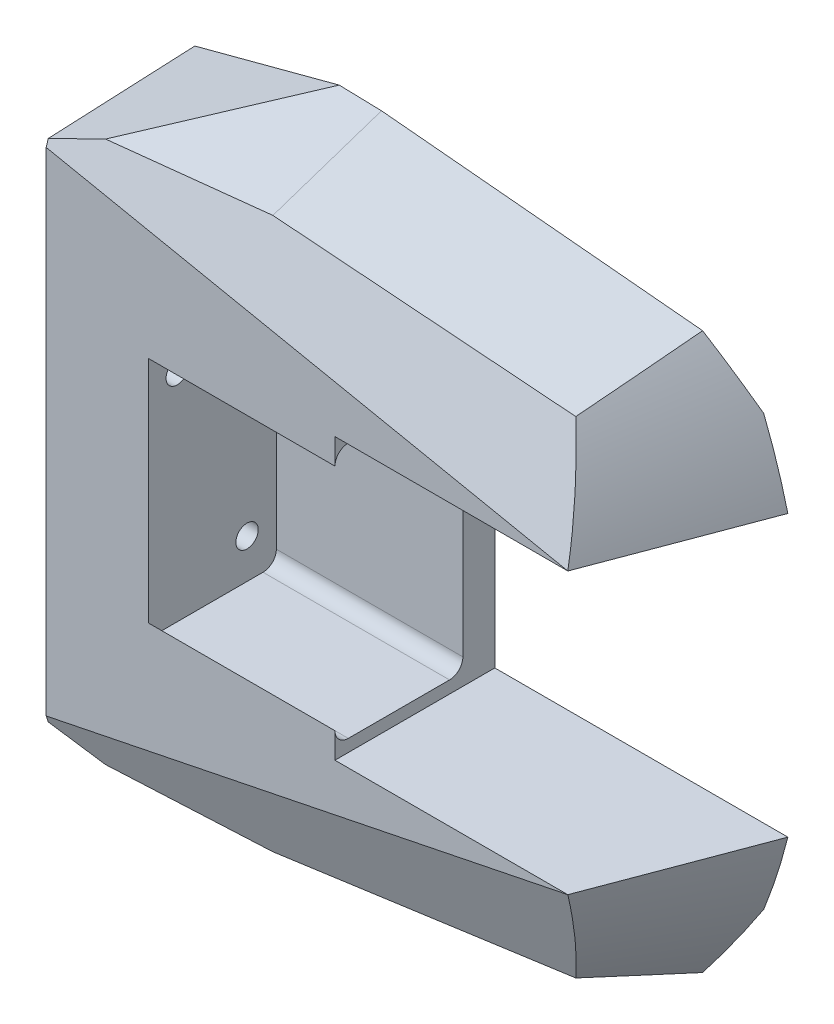
SolidWorks part; units mm, degrees
material "7075-O (SS)"
ref_plane "Top Plane" through (0, 0, 0) normal (0, 0, 1) x (1, 0, 0)
ref_plane "Front Plane" through (0, 0, 0) normal (0, 1, 0) x (1, 0, 0)
ref_plane "Right Plane" through (0, 0, 0) normal (1, 0, 0) x (0, 0, -1)
sketch "Sketch2" plane through (0, 0, 0) normal (0, 0, 1) x (1, 0, 0)
  line L0 (-50, 46.6303) -> (-41.2217, 50)
  line L1 (50, -50) -> (-50, -50)
  line L2 (50, -50) -> (50, 50)
  line L3 (50, 50) -> (-50, 50)
  line L4 (-50, -50) -> (-50, 50)
  line L5 (50, -50) -> (-50, 50) construction
  line L6 (50, 50) -> (-50, -50) construction
  line L7 (-10.1637, 50) -> (50, 42.6128)
  line L8 (-50, 0) -> (50, 0) construction
  line L9 (-10.1637, -50) -> (50, -42.6128)
  line L10 (-50, -46.6303) -> (-41.2217, -50)
  line L11 (50, 26.3007) -> (26.3007, 26.3007)
  line L12 (50, -26.3007) -> (26.3007, -26.3007)
  line L13 (26.3007, -26.3007) -> (26.3007, 26.3007)
  arc A0 (43.4207, 43.4207) -> (43.4207, -43.4207) centre (-44, 0) cw
  point P0 (0, 0)
  point P19 (50, -26.3007)
  point P20 (50, 26.3007)
  dimension "D1" = 100
  dimension "D2" = 100
  dimension "D3" = 69
  dimension "D4" = 3.3697
  dimension "D5" = 83
  dimension "D6" = 7.3872
  dimension "D7" = 44
extrude "Boss-Extrude1" add sketch "Sketch2" along normal blind 30 contours A0 L12 L13 L11 L7 L3 L0 L4 L10 L1 L9 region at (-7.835, 0, 0)
sketch "Sketch3" plane through (26.3007, 0, 0) normal (1, 0, 0) x (0, 0, -1)
  line L0 (-30, 26.3007) -> (0, 26.3007) construction
  line L1 (-30, -26.3007) -> (0, -26.3007)
  line L2 (-30, -26.3007) -> (-30, 26.3007)
  line L3 (-30, 26.3007) -> (0, 26.3007)
  line L4 (0, -26.3007) -> (0, 26.3007)
extrude "Cut-Extrude1" cut sketch "Sketch3" against normal blind 20
draft "Draft1" type of draft neutral plane draft angle 20 faces to draft 6 face at (-25.6927, 50, 15) face at (16.6285, 46.7103, 15) face at (46.9118, 34.9381, 15) face at (46.9118, -34.9381, 15) face at (-25.6927, -50, 15) face at (16.6285, -46.7103, 15) neutral plane through (0, 0, 30) neutral plane normal (0, 0, 1) parameters "D1"=20
sketch "Sketch5" plane through (-50, 0, 0) normal (-1, 0, 0) x (0, 0, 1)
  line L0 (0, -46.6303) -> (0, 46.6303) construction
  line L9 (0, 42) -> (23, 42)
  line L10 (0, 42) -> (0, -42)
  line L11 (0, -42) -> (23, -42)
  line L12 (28, 37) -> (28, -37)
  arc A0 (28, -37) -> (23, -42) centre (23, -37) cw
  arc A1 (28, 37) -> (23, 42) centre (23, 37) ccw
  point P15 (28, -42)
  point P18 (28, 42)
  dimension "D4" = 5
  dimension "D1" = 42
  dimension "D2" = 84
  dimension "D3" = 28
extrude "Cut-Extrude2" cut sketch "Sketch5" against normal blind 5
sketch "Sketch6" plane through (0, 0, 0) normal (0, 0, -1) x (-1, 0, 0)
  line L1 (45, 42) -> (10, 42)
  line L2 (45, 42) -> (45, -42)
  line L3 (45, -42) -> (10, -42)
  line L4 (5, 37) -> (5, -37)
  arc A0 (10, -42) -> (5, -37) centre (10, -37) cw
  arc A1 (10, 42) -> (5, 37) centre (10, 37) ccw
  point P7 (5, -42)
  point P10 (5, 42)
  dimension "D3" = 5
  dimension "D1" = 40
  dimension "D2" = 84
extrude "Cut-Extrude3" cut sketch "Sketch6" against normal blind 5
sketch "Sketch7" plane through (0, 0, 5) normal (0, 0, -1) x (-1, 0, 0)
  point P0 (29.9, 29.8957)
  point P3 (29.9, -29.8957)
hole_wizard "M6x1.0 Tapped Hole1" positions "Sketch7" profile "Sketch8" tap size "M6x1.0" standard "ANSI Metric"
sketch "Sketch8" plane through (-29.9, 29.8957, 5) normal (1, 0, 0) x (0, 1, 0)
  line L0 (0, 0) -> (0, 11.5022)
  line L1 (0, 11.5022) -> (2.5, 10)
  line L2 (2.5, 10) -> (2.5, 0)
  line L5 (2.5, 0) -> (0, 0)
  line L10 (0, 11.5022) -> (-2.5, 10) construction
  line L11 (0, -6.35) -> (0, 107.95) construction
  dimension "Tap Drill Dia." = 5
  dimension "Tap Drill Depth" = 10
  dimension "Drill Angle" = 118
cosmetic thread "Hole Thread1" parameters "D1"=12, "D2"=6
cosmetic thread "Hole Thread2" parameters "D1"=12, "D2"=6
sketch "Sketch9" plane through (0, 0, 0) normal (0, 0, -1) x (-1, 0, 0)
  line L0 (50, 46.6303) -> (-56.7679, 40.304)
  line L4 (50, 46.6303) -> (18.1671, 64.9129)
  line L5 (18.1671, 64.9129) -> (-51.4723, 56.583)
  arc A0 (-50.3888, 53.5662) -> (-61.2941, 26.3007) centre (44, 0) ccw construction
  arc A3 (-56.7679, 40.304) -> (-51.4723, 56.583) centre (56.438, 12.4787) cw
revolve "Cut-Revolve1" cut sketch "Sketch9" angle 20 about L0
sketch "Sketch11" plane through (0, 0, 0) normal (0, 0, -1) x (-1, 0, 0)
  line L0 (50, -46.6303) -> (-56.7679, -40.304)
  line L1 (50, -46.6303) -> (21.2236, -65.429)
  line L2 (21.2236, -65.429) -> (-53.454, -56.7727)
  arc A0 (-61.2941, -26.3007) -> (-50.3888, -53.5662) centre (44, 0) ccw construction
  arc A1 (-53.454, -56.7727) -> (-56.7679, -40.304) centre (59.1366, -25.5487) cw
revolve "Cut-Revolve2" cut sketch "Sketch11" angle 20 about L0 reverse direction yes
sketch "Sketch13" plane through (0, 0, 30) normal (0, 0, 1) x (1, 0, 0)
  line L0 (-50, 46.6303) -> (50, 26.3007)
  line L1 (50, 26.3007) -> (49.447, 52.16)
  line L2 (49.447, 52.16) -> (-50, 58.9949)
  line L3 (-50, 58.9949) -> (-50, 46.6303)
revolve "Cut-Revolve3" cut sketch "Sketch13" angle 20 about L0 reverse direction yes
sketch "Sketch14" plane through (0, 0, 30) normal (0, 0, 1) x (1, 0, 0)
  line L5 (50, -26.3007) -> (49.447, -52.16)
  line L6 (50, -26.3007) -> (-50, -46.6303)
  line L7 (-50, -46.6303) -> (-50, -58.9953)
  line L8 (-50, -58.9953) -> (49.447, -52.16)
  dimension "D1" = 12.365
revolve "Cut-Revolve4" cut sketch "Sketch14" angle 20 about L6 reverse direction yes
sketch "Sketch15" plane through (6.3007, 0, 0) normal (1, 0, 0) x (0, 0, -1)
  line L18 (-30, 0) -> (-30, -21.5)
  line L19 (-30, 26.3007) -> (-30, -26.3007) construction
  line L20 (-27.5, -24) -> (-8.5, -24)
  line L21 (-6, -21.5) -> (-6, 21.5)
  line L22 (-8.5, 24) -> (-27.5, 24)
  line L23 (-30, 21.5) -> (-30, 0)
  arc A0 (-8.5, -24) -> (-6, -21.5) centre (-8.5, -21.5) ccw
  arc A1 (-6, 21.5) -> (-8.5, 24) centre (-8.5, 21.5) ccw
  arc A2 (-27.5, 24) -> (-30, 21.5) centre (-27.5, 21.5) ccw
  arc A3 (-30, -21.5) -> (-27.5, -24) centre (-27.5, -21.5) ccw
  point P9 (-6, -24)
  point P14 (-30, 24)
  point P17 (-30, -24)
  dimension "D4" = 2.5
  dimension "D1" = 24
  dimension "D2" = 24
  dimension "D3" = 24
extrude "Cut-Extrude4" cut sketch "Sketch15" against normal blind 35
sketch "Sketch16" plane through (-28.6993, 0, 0) normal (1, 0, 0) x (0, 0, -1)
  point P0 (-11.498, -16.6054)
  point P3 (-24.602, 16.6054)
hole_wizard "M5x0.8 Tapped Hole1" positions "Sketch16" profile "Sketch17" tap size "M5x0.8" standard "ANSI Metric" end condition through all
sketch "Sketch17" plane through (-28.6993, -16.6054, 11.498) normal (0, 1, 0) x (0, 0, -1)
  line L0 (0, 0) -> (0, 21.3007)
  line L1 (0, 21.3007) -> (2.1, 21.3007)
  line L2 (2.1, 21.3007) -> (2.1, 0)
  line L5 (2.1, 0) -> (0, 0)
  line L11 (0, -6.35) -> (0, 107.95) construction
  dimension "Thru Tap Drill Dia." = 4.2
  dimension "Thru Tap Drill Depth" = 21.3007
cosmetic thread "Hole Thread3" parameters "D2"=5
cosmetic thread "Hole Thread4" parameters "D2"=5
sketch "Sketch19" plane through (-50, 0, 0) normal (-1, 0, 0) x (0, 0, 1)
  line L1 (0, 58.8905) -> (47.5161, 58.8905)
  line L2 (0, 58.8905) -> (0, -58.8905)
  line L3 (0, -58.8905) -> (47.5161, -58.8905)
  line L4 (47.5161, 58.8905) -> (47.5161, -58.8905)
revolve "Cut-Revolve5" cut sketch "Sketch19" angle 4 about L2 reverse direction yes
sketch "Sketch20" plane through (0, 0, 0) normal (0, 0, -1) x (-1, 0, 0)
  arc A0 (-56.7679, 40.304) -> (-61.2941, 26.3007) centre (44, 0) ccw construction
  arc A1 (-61.2941, -26.3007) -> (-56.7679, -40.304) centre (44, 0) ccw construction
  point P0 (-50.2687, 33.3791)
  point P2 (-50.2687, -33.3791)
  point P4 (-36.2687, -33.3791)
  point P6 (-22.2687, -33.3791)
  point P8 (-36.2687, 33.3791)
  point P10 (-22.2687, 33.3791)
  point P16 (-59.2687, 33.3791)
  point P20 (-59.2687, -33.3791)
  dimension "D1" = 9
  dimension "D2" = 14
  dimension "D3" = 14
  dimension "D4" = 9
  dimension "D5" = 14
  dimension "D6" = 14
  dimension "D7" = 66.7583
hole_wizard "CSK for M5 Flat Head Machine Screw1" positions "Sketch20" profile "Sketch21" countersink size "M5" standard "ANSI Metric"
sketch "Sketch21" plane through (50.2687, 33.3791, 0) normal (1, 0, 0) x (0, 1, 0)
  line L0 (0, 0) -> (0, 11.6524)
  line L1 (0, 11.6524) -> (2.75, 10)
  line L2 (2.75, 10) -> (2.75, 2.45)
  line L3 (2.75, 2.45) -> (5.2, 0)
  line L5 (5.2, 0) -> (0, 0)
  line L6 (-2.75, 2.45) -> (-5.2, 0) construction
  line L10 (0, 11.6524) -> (-2.75, 10) construction
  line L11 (0, -6.35) -> (0, 107.95) construction
  dimension "Hole Dia." = 5.5
  dimension "Hole Depth" = 10
  dimension "Near C'Sink Dia." = 10.4
  dimension "Near C'Sink Angle" = 90
  dimension "Drill Angle" = 118
